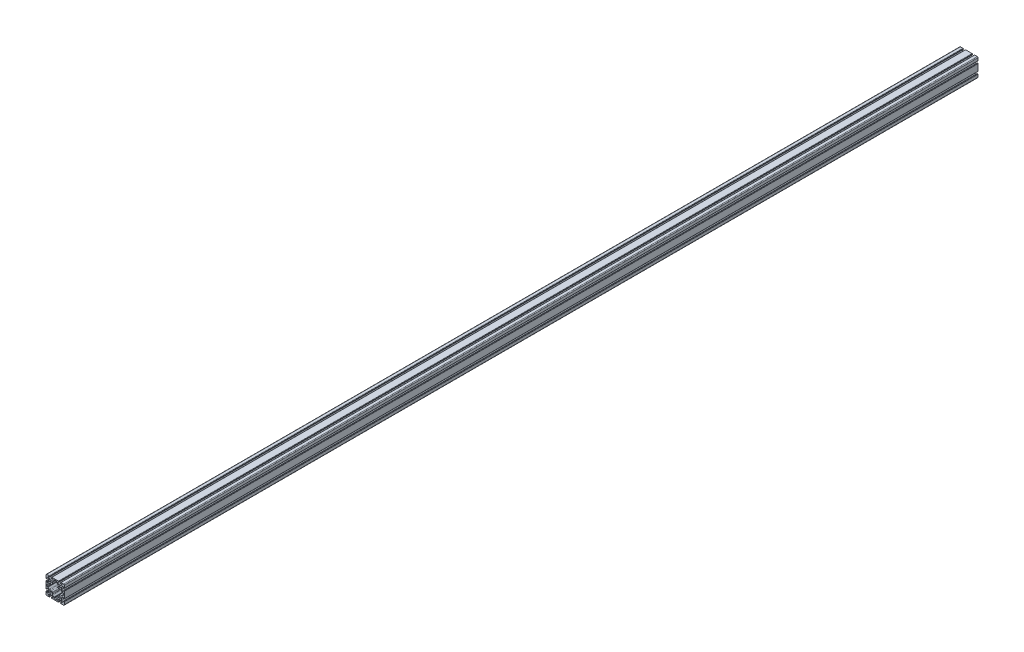
SolidWorks part; units mm, degrees
material "6061 Alloy"
ref_plane "Front Plane" through (0, 0, 0) normal (0, 0, 1) x (1, 0, 0)
ref_plane "Top Plane" through (0, 0, 0) normal (0, 1, 0) x (1, 0, 0)
ref_plane "Right Plane" through (0, 0, 0) normal (1, 0, 0) x (0, 0, -1)
sketch "Sketch1" plane through (0, 0, 0) normal (0, 0, 1) x (1, 0, 0)
  line L0 (0, -40) -> (0, 40) construction
  line L1 (0, 0) -> (-43.5804, 43.5804) construction
  line L2 (-20, 20) -> (-47.7323, 20) construction
  line L3 (-20, 20) -> (3.796, 43.796) construction
  line L4 (-20, 20) -> (-20, 43.5758) construction
  line L5 (-20, -27.7) -> (-20, -47.5576) construction
  line L131 (29.0912, 26.0365) -> (33.0827, 30.028)
  line L132 (27.7, 17.3222) -> (27.7, 22.6778)
  line L133 (29.0912, 13.9635) -> (33.0827, 9.972)
  line L134 (33.6201, 9.7494) -> (34.11, 9.7494)
  line L135 (35.68, 11.3194) -> (35.68, 14.2221)
  line L136 (37.25, 15.7921) -> (38.43, 15.7921)
  line L137 (40, 14.2221) -> (40, 7.0214)
  line L138 (40, 7.0214) -> (40, -7.0214)
  line L139 (40, -7.0214) -> (40, -14.2221)
  line L140 (38.43, -15.7921) -> (37.25, -15.7921)
  line L141 (35.68, -14.2221) -> (35.68, -11.3194)
  line L142 (33.6201, -9.7494) -> (34.11, -9.7494)
  line L143 (29.0912, -13.9635) -> (33.0827, -9.972)
  line L144 (27.7, -22.6778) -> (27.7, -17.3222)
  line L145 (29.0912, -26.0365) -> (33.0827, -30.028)
  line L146 (33.6201, -30.2506) -> (34.11, -30.2506)
  line L147 (35.68, -28.6806) -> (35.68, -25.7779)
  line L148 (37.25, -24.2079) -> (38.43, -24.2079)
  line L149 (40, -25.7779) -> (40, -33.0259)
  line L150 (40, -33.0259) -> (40, -36.83)
  line L151 (36.83, -40) -> (32.9998, -40)
  line L152 (32.9998, -40) -> (25.5696, -40)
  line L153 (23.9996, -38.43) -> (23.9996, -37.25)
  line L154 (25.5696, -35.68) -> (28.4723, -35.68)
  line L155 (30.0413, -34.0552) -> (30.0171, -33.3605)
  line L156 (29.7949, -32.8496) -> (26.0365, -29.0912)
  line L157 (17.3222, -27.7) -> (22.6778, -27.7)
  line L158 (10.035, -33.0197) -> (13.9635, -29.0912)
  line L159 (9.8124, -33.8926) -> (9.8124, -33.5571)
  line L160 (11.3824, -35.4626) -> (14.4246, -35.4626)
  line L161 (15.9946, -37.0326) -> (15.9946, -38.43)
  line L162 (14.4246, -40) -> (6.9987, -40)
  line L163 (6.9987, -40) -> (-6.9987, -40)
  line L164 (-6.9987, -40) -> (-14.4292, -40)
  line L165 (-15.9992, -38.43) -> (-15.9992, -37.25)
  line L166 (-14.4292, -35.68) -> (-11.5265, -35.68)
  line L167 (-9.9574, -34.0552) -> (-9.9816, -33.3618)
  line L168 (-10.2038, -32.8509) -> (-13.9635, -29.0912)
  line L169 (-22.6778, -27.7) -> (-17.3222, -27.7)
  line L170 (-30.028, -33.0827) -> (-26.0365, -29.0912)
  line L171 (-30.2506, -34.11) -> (-30.2506, -33.6201)
  line L172 (-28.6806, -35.68) -> (-25.7231, -35.68)
  line L173 (-24.1531, -37.25) -> (-24.1531, -38.43)
  line L174 (-25.7231, -40) -> (-33, -40)
  line L175 (-33, -40) -> (-36.83, -40)
  line L176 (-40, -36.83) -> (-40, -33.0191)
  line L177 (-40, -33.0191) -> (-40, -25.591)
  line L178 (-38.43, -24.021) -> (-37.25, -24.021)
  line L179 (-35.68, -28.4937) -> (-35.68, -25.591)
  line L180 (-34.0552, -30.0627) -> (-33.3827, -30.0392)
  line L181 (-32.8718, -29.8171) -> (-29.0912, -26.0365)
  line L182 (-27.7, -22.6778) -> (-27.7, -17.3222)
  line L183 (-29.0912, -13.9635) -> (-33.0827, -9.972)
  line L184 (-34.11, -9.7494) -> (-33.6201, -9.7494)
  line L185 (-35.68, -11.3194) -> (-35.68, -14.4473)
  line L186 (-38.43, -16.0173) -> (-37.25, -16.0173)
  line L187 (-40, -14.4473) -> (-40, -7.0169)
  line L188 (-40, -7.0169) -> (-40, 7.0169)
  line L189 (-40, 7.0169) -> (-40, 14.1348)
  line L190 (-38.1948, 15.94) -> (-36.9772, 15.94)
  line L191 (-35.68, 11.3194) -> (-35.68, 14.6428)
  line L192 (-34.11, 9.7494) -> (-33.6201, 9.7494)
  line L193 (-33.0827, 9.972) -> (-29.0912, 13.9635)
  line L194 (-27.7, 17.3222) -> (-27.7, 22.6778)
  line L195 (-29.0912, 26.0365) -> (-33.0827, 30.028)
  line L196 (-34.11, 30.2506) -> (-33.6201, 30.2506)
  line L197 (-35.68, 28.6806) -> (-35.68, 25.3572)
  line L198 (-38.1948, 24.06) -> (-36.9772, 24.06)
  line L199 (-40, 25.8652) -> (-40, 33.3181)
  line L200 (-40, 33.3181) -> (-40, 36.83)
  line L201 (-36.83, 40) -> (-33.0314, 40)
  line L202 (-33.0314, 40) -> (-25.8652, 40)
  line L203 (-24.06, 36.9772) -> (-24.06, 38.1948)
  line L204 (-25.3572, 35.68) -> (-28.7018, 35.68)
  line L205 (-30.285, 33.6069) -> (-30.285, 34.0968)
  line L206 (-30.0961, 33.1508) -> (-26.0365, 29.0912)
  line L207 (-22.6778, 27.7) -> (-17.3222, 27.7)
  line L208 (-13.9635, 29.0912) -> (-9.9039, 33.1508)
  line L209 (-9.715, 33.6069) -> (-9.715, 34.0968)
  line L210 (-14.6428, 35.68) -> (-11.2982, 35.68)
  line L211 (-15.94, 36.9772) -> (-15.94, 38.1948)
  line L212 (-14.1348, 40) -> (-6.9844, 40)
  line L213 (-6.9844, 40) -> (6.9844, 40)
  line L214 (6.9844, 40) -> (14.1348, 40)
  line L215 (15.94, 36.9772) -> (15.94, 38.1948)
  line L216 (14.6428, 35.68) -> (11.2982, 35.68)
  line L217 (9.715, 33.6069) -> (9.715, 34.0968)
  line L218 (9.9039, 33.1508) -> (13.9635, 29.0912)
  line L219 (17.3222, 27.7) -> (22.6778, 27.7)
  line L220 (26.0365, 29.0912) -> (30.028, 33.0827)
  line L221 (30.2506, 33.6201) -> (30.2506, 34.11)
  line L222 (25.5409, 35.679) -> (28.6258, 35.679)
  line L223 (23.9709, 37.249) -> (23.9709, 38.43)
  line L224 (25.5409, 40) -> (36.83, 40)
  line L226 (40, 36.83) -> (40, 32.9339)
  line L227 (40, 32.9339) -> (40, 25.7779)
  line L228 (38.43, 24.2079) -> (37.0956, 24.2079)
  line L229 (35.5256, 25.7779) -> (35.5256, 28.6806)
  line L230 (33.6201, 30.2506) -> (33.9556, 30.2506)
  line L231 (17.07, 12.32) -> (22.6578, 12.32)
  line L232 (26.0165, 10.9288) -> (31.1439, 5.8014)
  line L233 (32.0419, 5.4294) -> (34.41, 5.4294)
  line L234 (35.68, -4.1594) -> (35.68, 4.1594)
  line L235 (32.0419, -5.4294) -> (34.41, -5.4294)
  line L236 (26.0165, -10.9288) -> (31.1439, -5.8014)
  line L237 (17.07, -12.32) -> (22.6578, -12.32)
  line L238 (12.32, -22.6578) -> (12.32, -17.07)
  line L239 (5.8014, -31.1439) -> (10.9288, -26.0165)
  line L240 (5.4294, -34.41) -> (5.4294, -32.0419)
  line L241 (-4.1594, -35.68) -> (4.1594, -35.68)
  line L242 (-5.4294, -34.41) -> (-5.4294, -32.0419)
  line L243 (-5.8014, -31.1439) -> (-10.9288, -26.0165)
  line L244 (-12.32, -22.6578) -> (-12.32, -17.07)
  line L245 (-22.6578, -12.32) -> (-17.07, -12.32)
  line L246 (-26.0165, -10.9288) -> (-31.1439, -5.8014)
  line L247 (-34.41, -5.4294) -> (-32.0419, -5.4294)
  line L248 (-35.68, -4.1594) -> (-35.68, 4.1594)
  line L249 (-34.41, 5.4294) -> (-32.0419, 5.4294)
  line L250 (-31.1439, 5.8014) -> (-26.0165, 10.9288)
  line L251 (-22.6578, 12.32) -> (-17.07, 12.32)
  line L252 (-12.32, 17.07) -> (-12.32, 22.6578)
  line L253 (-10.9288, 26.0165) -> (-5.8014, 31.1439)
  line L254 (-5.4294, 32.0419) -> (-5.4294, 34.41)
  line L255 (-4.1594, 35.68) -> (4.1594, 35.68)
  line L256 (5.4294, 32.0419) -> (5.4294, 34.41)
  line L257 (5.8014, 31.1439) -> (10.9288, 26.0165)
  line L258 (12.32, 17.07) -> (12.32, 22.6578)
  line L260 (-40, 0) -> (40, 0) construction
  circle A116 centre (-20, 20) radius 3.4
  circle A117 centre (20, 20) radius 3.4
  circle A118 centre (20, -20) radius 3.4
  circle A119 centre (-20, -20) radius 3.4
  arc A120 (29.0912, 26.0365) -> (27.7, 22.6778) centre (32.45, 22.6778) ccw
  arc A121 (27.7, 17.3222) -> (29.0912, 13.9635) centre (32.45, 17.3222) ccw
  arc A122 (33.0827, 9.972) -> (33.6201, 9.7494) centre (33.6201, 10.5094) ccw
  arc A123 (34.11, 9.7494) -> (35.68, 11.3194) centre (34.11, 11.3194) ccw
  arc A124 (37.25, 15.7921) -> (35.68, 14.2221) centre (37.25, 14.2221) ccw
  arc A125 (40, 14.2221) -> (38.43, 15.7921) centre (38.43, 14.2221) ccw
  arc A126 (38.43, -15.7921) -> (40, -14.2221) centre (38.43, -14.2221) ccw
  arc A127 (35.68, -14.2221) -> (37.25, -15.7921) centre (37.25, -14.2221) ccw
  arc A128 (35.68, -11.3194) -> (34.11, -9.7494) centre (34.11, -11.3194) ccw
  arc A129 (33.6201, -9.7494) -> (33.0827, -9.972) centre (33.6201, -10.5094) ccw
  arc A130 (29.0912, -13.9635) -> (27.7, -17.3222) centre (32.45, -17.3222) ccw
  arc A131 (27.7, -22.6778) -> (29.0912, -26.0365) centre (32.45, -22.6778) ccw
  arc A132 (33.0827, -30.028) -> (33.6201, -30.2506) centre (33.6201, -29.4906) ccw
  arc A133 (34.11, -30.2506) -> (35.68, -28.6806) centre (34.11, -28.6806) ccw
  arc A134 (37.25, -24.2079) -> (35.68, -25.7779) centre (37.25, -25.7779) ccw
  arc A135 (40, -25.7779) -> (38.43, -24.2079) centre (38.43, -25.7779) ccw
  arc A136 (36.83, -40) -> (40, -36.83) centre (36.83, -36.83) ccw
  arc A137 (23.9996, -38.43) -> (25.5696, -40) centre (25.5696, -38.43) ccw
  arc A138 (25.5696, -35.68) -> (23.9996, -37.25) centre (25.5696, -37.25) ccw
  arc A139 (28.4723, -35.68) -> (30.0413, -34.0552) centre (28.4723, -34.11) ccw
  arc A140 (30.0171, -33.3605) -> (29.7949, -32.8496) centre (29.2575, -33.387) ccw
  arc A141 (26.0365, -29.0912) -> (22.6778, -27.7) centre (22.6778, -32.45) ccw
  arc A142 (17.3222, -27.7) -> (13.9635, -29.0912) centre (17.3222, -32.45) ccw
  arc A143 (10.035, -33.0197) -> (9.8124, -33.5571) centre (10.5724, -33.5571) ccw
  arc A144 (9.8124, -33.8926) -> (11.3824, -35.4626) centre (11.3824, -33.8926) ccw
  arc A145 (15.9946, -37.0326) -> (14.4246, -35.4626) centre (14.4246, -37.0326) ccw
  arc A146 (14.4246, -40) -> (15.9946, -38.43) centre (14.4246, -38.43) ccw
  arc A147 (-15.9992, -38.43) -> (-14.4292, -40) centre (-14.4292, -38.43) ccw
  arc A148 (-14.4292, -35.68) -> (-15.9992, -37.25) centre (-14.4292, -37.25) ccw
  arc A149 (-11.5265, -35.68) -> (-9.9574, -34.0552) centre (-11.5265, -34.11) ccw
  arc A150 (-9.9816, -33.3618) -> (-10.2038, -32.8509) centre (-10.7412, -33.3883) ccw
  arc A151 (-13.9635, -29.0912) -> (-17.3222, -27.7) centre (-17.3222, -32.45) ccw
  arc A152 (-22.6778, -27.7) -> (-26.0365, -29.0912) centre (-22.6778, -32.45) ccw
  arc A153 (-30.028, -33.0827) -> (-30.2506, -33.6201) centre (-29.4906, -33.6201) ccw
  arc A154 (-30.2506, -34.11) -> (-28.6806, -35.68) centre (-28.6806, -34.11) ccw
  arc A155 (-24.1531, -37.25) -> (-25.7231, -35.68) centre (-25.7231, -37.25) ccw
  arc A156 (-25.7231, -40) -> (-24.1531, -38.43) centre (-25.7231, -38.43) ccw
  arc A157 (-40, -36.83) -> (-36.83, -40) centre (-36.83, -36.83) ccw
  arc A158 (-38.43, -24.021) -> (-40, -25.591) centre (-38.43, -25.591) ccw
  arc A159 (-35.68, -25.591) -> (-37.25, -24.021) centre (-37.25, -25.591) ccw
  arc A160 (-35.68, -28.4937) -> (-34.0552, -30.0627) centre (-34.11, -28.4937) ccw
  arc A161 (-33.3827, -30.0392) -> (-32.8718, -29.8171) centre (-33.4092, -29.2797) ccw
  arc A162 (-29.0912, -26.0365) -> (-27.7, -22.6778) centre (-32.45, -22.6778) ccw
  arc A163 (-27.7, -17.3222) -> (-29.0912, -13.9635) centre (-32.45, -17.3222) ccw
  arc A164 (-33.0827, -9.972) -> (-33.6201, -9.7494) centre (-33.6201, -10.5094) ccw
  arc A165 (-34.11, -9.7494) -> (-35.68, -11.3194) centre (-34.11, -11.3194) ccw
  arc A166 (-37.25, -16.0173) -> (-35.68, -14.4473) centre (-37.25, -14.4473) ccw
  arc A167 (-40, -14.4473) -> (-38.43, -16.0173) centre (-38.43, -14.4473) ccw
  arc A168 (-38.1948, 15.94) -> (-40, 14.1348) centre (-38.1948, 14.1348) ccw
  arc A169 (-35.68, 14.6428) -> (-36.9772, 15.94) centre (-36.9772, 14.6428) ccw
  arc A170 (-35.68, 11.3194) -> (-34.11, 9.7494) centre (-34.11, 11.3194) ccw
  arc A171 (-33.6201, 9.7494) -> (-33.0827, 9.972) centre (-33.6201, 10.5094) ccw
  arc A172 (-29.0912, 13.9635) -> (-27.7, 17.3222) centre (-32.45, 17.3222) ccw
  arc A173 (-27.7, 22.6778) -> (-29.0912, 26.0365) centre (-32.45, 22.6778) ccw
  arc A174 (-33.0827, 30.028) -> (-33.6201, 30.2506) centre (-33.6201, 29.4906) ccw
  arc A175 (-34.11, 30.2506) -> (-35.68, 28.6806) centre (-34.11, 28.6806) ccw
  arc A176 (-36.9772, 24.06) -> (-35.68, 25.3572) centre (-36.9772, 25.3572) ccw
  arc A177 (-40, 25.8652) -> (-38.1948, 24.06) centre (-38.1948, 25.8652) ccw
  arc A178 (-36.83, 40) -> (-40, 36.83) centre (-36.83, 36.83) ccw
  arc A179 (-24.06, 38.1948) -> (-25.8652, 40) centre (-25.8652, 38.1948) ccw
  arc A180 (-25.3572, 35.68) -> (-24.06, 36.9772) centre (-25.3572, 36.9772) ccw
  arc A181 (-28.7018, 35.68) -> (-30.285, 34.0968) centre (-28.7018, 34.0968) ccw
  arc A182 (-30.285, 33.6069) -> (-30.0961, 33.1508) centre (-29.6399, 33.6069) ccw
  arc A183 (-26.0365, 29.0912) -> (-22.6778, 27.7) centre (-22.6778, 32.45) ccw
  arc A184 (-17.3222, 27.7) -> (-13.9635, 29.0912) centre (-17.3222, 32.45) ccw
  arc A185 (-9.9039, 33.1508) -> (-9.715, 33.6069) centre (-10.3601, 33.6069) ccw
  arc A186 (-9.715, 34.0968) -> (-11.2982, 35.68) centre (-11.2982, 34.0968) ccw
  arc A187 (-15.94, 36.9772) -> (-14.6428, 35.68) centre (-14.6428, 36.9772) ccw
  arc A188 (-14.1348, 40) -> (-15.94, 38.1948) centre (-14.1348, 38.1948) ccw
  arc A189 (15.94, 38.1948) -> (14.1348, 40) centre (14.1348, 38.1948) ccw
  arc A190 (14.6428, 35.68) -> (15.94, 36.9772) centre (14.6428, 36.9772) ccw
  arc A191 (11.2982, 35.68) -> (9.715, 34.0968) centre (11.2982, 34.0968) ccw
  arc A192 (9.715, 33.6069) -> (9.9039, 33.1508) centre (10.3601, 33.6069) ccw
  arc A193 (13.9635, 29.0912) -> (17.3222, 27.7) centre (17.3222, 32.45) ccw
  arc A194 (22.6778, 27.7) -> (26.0365, 29.0912) centre (22.6778, 32.45) ccw
  arc A195 (30.028, 33.0827) -> (30.2506, 33.6201) centre (29.4906, 33.6201) ccw
  arc A196 (30.2506, 34.11) -> (28.6258, 35.679) centre (28.6806, 34.11) ccw
  arc A197 (23.9709, 37.249) -> (25.5409, 35.679) centre (25.5409, 37.249) ccw
  arc A198 (25.5409, 40) -> (23.9709, 38.43) centre (25.5409, 38.43) ccw
  arc A199 (40, 36.83) -> (36.83, 40) centre (36.83, 36.83) ccw
  arc A200 (38.43, 24.2079) -> (40, 25.7779) centre (38.43, 25.7779) ccw
  arc A201 (35.5256, 25.7779) -> (37.0956, 24.2079) centre (37.0956, 25.7779) ccw
  arc A202 (35.5256, 28.6806) -> (33.9556, 30.2506) centre (33.9556, 28.6806) ccw
  arc A203 (33.6201, 30.2506) -> (33.0827, 30.028) centre (33.6201, 29.4906) ccw
  arc A204 (26.0165, 10.9288) -> (22.6578, 12.32) centre (22.6578, 7.57) ccw
  arc A205 (31.1439, 5.8014) -> (32.0419, 5.4294) centre (32.0419, 6.6994) ccw
  arc A206 (35.68, 4.1594) -> (34.41, 5.4294) centre (34.41, 4.1594) ccw
  arc A207 (34.41, -5.4294) -> (35.68, -4.1594) centre (34.41, -4.1594) ccw
  arc A208 (32.0419, -5.4294) -> (31.1439, -5.8014) centre (32.0419, -6.6994) ccw
  arc A209 (22.6578, -12.32) -> (26.0165, -10.9288) centre (22.6578, -7.57) ccw
  arc A210 (17.07, -12.32) -> (12.32, -17.07) centre (17.07, -17.07) ccw
  arc A211 (10.9288, -26.0165) -> (12.32, -22.6578) centre (7.57, -22.6578) ccw
  arc A212 (5.8014, -31.1439) -> (5.4294, -32.0419) centre (6.6994, -32.0419) ccw
  arc A213 (4.1594, -35.68) -> (5.4294, -34.41) centre (4.1594, -34.41) ccw
  arc A214 (-5.4294, -34.41) -> (-4.1594, -35.68) centre (-4.1594, -34.41) ccw
  arc A215 (-5.4294, -32.0419) -> (-5.8014, -31.1439) centre (-6.6994, -32.0419) ccw
  arc A216 (-12.32, -22.6578) -> (-10.9288, -26.0165) centre (-7.57, -22.6578) ccw
  arc A217 (-12.32, -17.07) -> (-17.07, -12.32) centre (-17.07, -17.07) ccw
  arc A218 (-26.0165, -10.9288) -> (-22.6578, -12.32) centre (-22.6578, -7.57) ccw
  arc A219 (-31.1439, -5.8014) -> (-32.0419, -5.4294) centre (-32.0419, -6.6994) ccw
  arc A220 (-35.68, -4.1594) -> (-34.41, -5.4294) centre (-34.41, -4.1594) ccw
  arc A221 (-34.41, 5.4294) -> (-35.68, 4.1594) centre (-34.41, 4.1594) ccw
  arc A222 (-32.0419, 5.4294) -> (-31.1439, 5.8014) centre (-32.0419, 6.6994) ccw
  arc A223 (-22.6578, 12.32) -> (-26.0165, 10.9288) centre (-22.6578, 7.57) ccw
  arc A224 (-17.07, 12.32) -> (-12.32, 17.07) centre (-17.07, 17.07) ccw
  arc A225 (-10.9288, 26.0165) -> (-12.32, 22.6578) centre (-7.57, 22.6578) ccw
  arc A226 (-5.8014, 31.1439) -> (-5.4294, 32.0419) centre (-6.6994, 32.0419) ccw
  arc A227 (-4.1594, 35.68) -> (-5.4294, 34.41) centre (-4.1594, 34.41) ccw
  arc A228 (5.4294, 34.41) -> (4.1594, 35.68) centre (4.1594, 34.41) ccw
  arc A229 (5.4294, 32.0419) -> (5.8014, 31.1439) centre (6.6994, 32.0419) ccw
  arc A230 (12.32, 22.6578) -> (10.9288, 26.0165) centre (7.57, 22.6578) ccw
  arc A231 (12.32, 17.07) -> (17.07, 12.32) centre (17.07, 17.07) ccw
  dimension "D8" = 6.8
  dimension "D1" = 80
  dimension "D2" = 40
  dimension "D3" = 20
  dimension "D4" = 20.57
  dimension "D5" = 4.32
  dimension "D6" = 4.32
  dimension "D7" = 8.12
  dimension "D9" = 4.32
  dimension "D10" = 12.3
extrude "Extrude1" add sketch "Sketch1" against normal blind 4000
